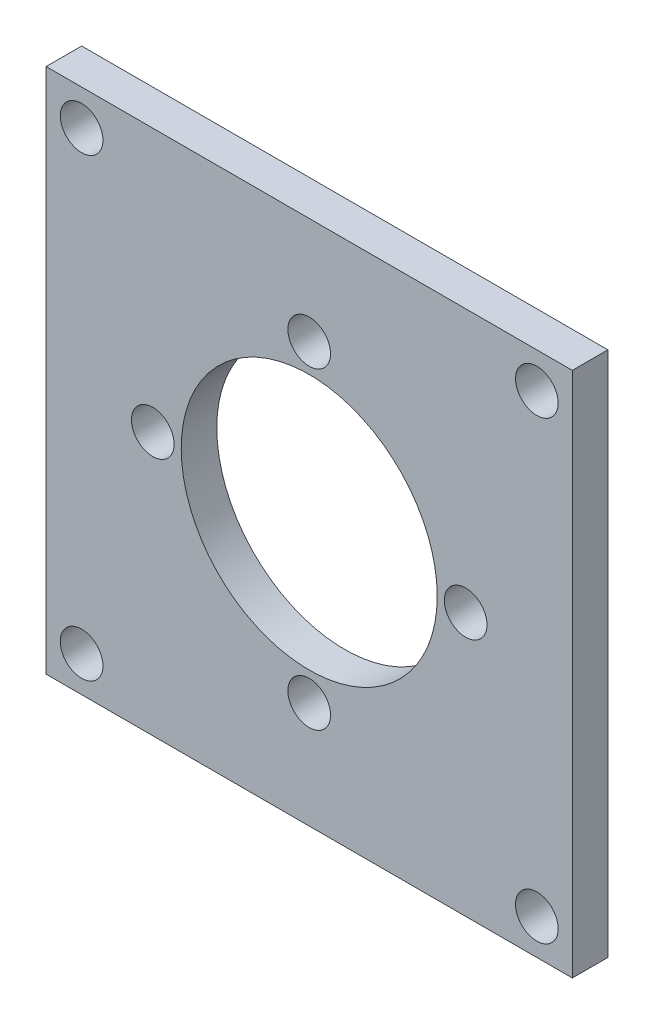
SolidWorks part; units mm, degrees
ref_plane "Front Plane" through (0, 0, 0) normal (0, 0, 1) x (1, 0, 0)
ref_plane "Top Plane" through (0, 0, 0) normal (0, 1, 0) x (1, 0, 0)
ref_plane "Right Plane" through (0, 0, 0) normal (1, 0, 0) x (0, 0, -1)
sketch "Sketch1" plane through (0, 0, 0) normal (0, 0, 1) x (1, 0, 0)
  line L1 (-18.5, 18.5) -> (18.5, 18.5)
  line L2 (-18.5, 18.5) -> (-18.5, -18.5)
  line L3 (-18.5, -18.5) -> (18.5, -18.5)
  line L4 (18.5, 18.5) -> (18.5, -18.5)
  line L5 (-18.5, 18.5) -> (18.5, -18.5) construction
  line L6 (-18.5, -18.5) -> (18.5, 18.5) construction
  point P0 (0, 0)
  dimension "D1" = 37
  dimension "D2" = 37
extrude "Boss-Extrude1" add sketch "Sketch1" along normal blind 2.5
sketch "Sketch3" plane through (0, 0, 2.5) normal (0, 0, 1) x (1, 0, 0)
  circle A0 centre (0, 0) radius 9
  dimension "D1" = 18
extrude "Cut-Extrude1" cut sketch "Sketch3" against normal through all
sketch "Sketch4" plane through (0, 0, 2.5) normal (0, 0, 1) x (1, 0, 0)
  line L0 (0, 11) -> (0, -11)
  line L1 (-11, 0) -> (11, 0)
  point P4 (0, 0)
  point P8 (0, 0)
  dimension "D1" = 22
  dimension "D2" = 22
sketch "Sketch9" plane through (0, 0, 2.5) normal (0, 0, 1) x (1, 0, 0)
  line L0 (-18.5, 18.5) -> (18.5, -18.5) construction
  line L1 (-18.5, -18.5) -> (18.5, 18.5) construction
  point P4 (-16.0039, 16.0039)
  point P5 (16.0039, -16.0039)
  point P10 (16.0039, 16.0039)
  point P11 (-16.0039, -16.0039)
  dimension "D1" = 3.53
  dimension "D2" = 3.53
  dimension "D3" = 3.53
  dimension "D4" = 3.53
sketch "Sketch11" plane through (0, 0, 2.5) normal (0, 0, 1) x (1, 0, 0)
  circle A0 centre (-16.0039, 16.0039) radius 1.5
  circle A1 centre (16.0039, 16.0039) radius 1.5
  circle A2 centre (-16.0039, -16.0039) radius 1.5
  circle A3 centre (16.0039, -16.0039) radius 1.5
  dimension "D1" = 3
  dimension "D2" = 3
  dimension "D3" = 3
  dimension "D4" = 3
extrude "Cut-Extrude2" cut sketch "Sketch11" against normal through all
sketch "Sketch12" plane through (0, 0, 2.5) normal (0, 0, 1) x (1, 0, 0)
  circle A0 centre (0, 11) radius 1.5
  circle A1 centre (11, 0) radius 1.5
  circle A3 centre (-11, 0) radius 1.5
  circle A4 centre (0, -11) radius 1.5
  point P9 (0, 0)
  point P10 (0, 0)
  point P11 (-0.0963, -11.2067)
  point P12 (0, -11)
  point P14 (-11, 0)
  point P16 (11, 0)
  dimension "D1" = 3
extrude "Cut-Extrude3" cut sketch "Sketch12" against normal through all
